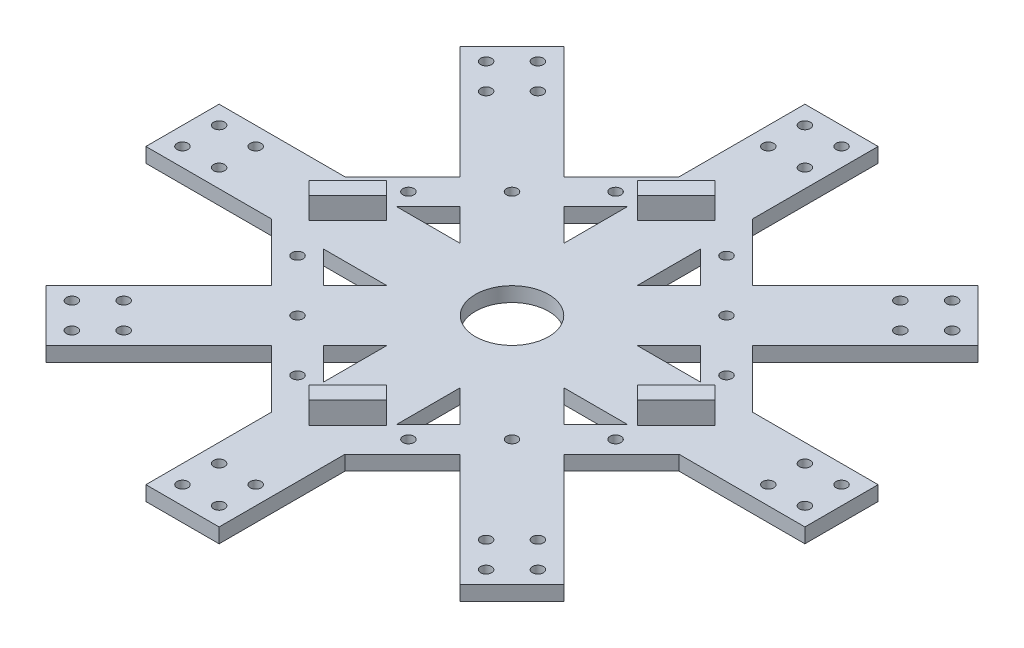
SolidWorks part; units mm, degrees
ref_plane "Front Plane" through (0, 0, 0) normal (0, 0, 1) x (1, 0, 0)
ref_plane "Top Plane" through (0, 0, 0) normal (0, 1, 0) x (1, 0, 0)
ref_plane "Right Plane" through (0, 0, 0) normal (1, 0, 0) x (0, 0, -1)
sketch "Sketch1" plane through (0, 0, 0) normal (0, 1, 0) x (1, 0, 0)
  line L0 (20, 100) -> (100, 100)
  line L1 (0, 0) -> (20, 0)
  line L2 (0, 0) -> (0, 80)
  line L3 (0, 180) -> (20, 180)
  line L4 (20, 0) -> (20, 80)
  line L5 (-80, 100) -> (0, 100)
  line L6 (-80, 100) -> (-80, 80)
  line L7 (-80, 80) -> (0, 80)
  line L8 (100, 100) -> (100, 80)
  line L9 (0, 100) -> (0, 180)
  line L10 (20, 80) -> (100, 80)
  line L11 (20, 100) -> (20, 180)
  line L12 (-40, 100) -> (0, 140) construction
  line L13 (20, 140) -> (60, 100) construction
  line L14 (60, 80) -> (20, 40) construction
  line L15 (0, 40) -> (-40, 80) construction
  line L16 (0, 48.4853) -> (-31.5147, 80)
  line L17 (51.5147, 80) -> (20, 48.4853)
  line L18 (20, 131.5147) -> (51.5147, 100)
  line L19 (-31.5147, 100) -> (0, 131.5147)
  line L20 (0, 34.3431) -> (-45.6569, 80)
  line L21 (65.6569, 80) -> (20, 34.3431)
  line L22 (20, 145.6569) -> (65.6569, 100)
  line L23 (-45.6569, 100) -> (0, 145.6569)
  line L24 (-2.8284, 37.1716) -> (-42.8284, 77.1716) construction
  line L25 (-35.7574, 95.7574) -> (4.2426, 135.7574) construction
  line L26 (15.7574, 135.7574) -> (55.7574, 95.7574) construction
  line L27 (55.7574, 84.2426) -> (15.7574, 44.2426) construction
  line L28 (4.2426, 44.2426) -> (-35.7574, 84.2426) construction
  line L29 (62.8284, 77.1716) -> (22.8284, 37.1716) construction
  line L30 (22.8284, 142.8284) -> (62.8284, 102.8284) construction
  line L31 (-42.8284, 102.8284) -> (-2.8284, 142.8284) construction
  circle A0 centre (10, 90) radius 1.5
  point P24 (10, 180)
  point P25 (100, 90)
  dimension "D13" = 3
  dimension "D2" = 180
  dimension "D3" = 180
  dimension "D4" = 20
  dimension "D7" = 40
  dimension "D8" = 40
  dimension "D9" = 40
  dimension "D10" = 40
  dimension "D11" = 6
  dimension "D12" = 4
extrude "Base" add sketch "Sketch1" along normal blind 4 contours L0 L11 L3 L9 L5 L6 L7 L2 L1 L4 L10 L8 | L23 L5 L19 L9 | L22 L11 L18 L0 | L20 L2 L16 L7 | L21 L10 L17 L4 region at (35.7574, 0, -97.4544) region at (39.5089, 0, -119.5089) region at (39.5089, 0, -60.4911) region at (-19.5089, 0, -119.5089) region at (-19.5089, 0, -60.4911)
sketch "Sketch2" plane through (0, 4, 0) normal (0, 1, 0) x (1, 0, 0)
  line L0 (40.5824, 165.4836) -> (-65.4836, 59.4176) construction
  line L1 (-65.4836, 59.4176) -> (-20.5824, 14.5164) construction
  line L2 (-20.5824, 14.5164) -> (85.4836, 120.5824) construction
  line L3 (85.4836, 120.5824) -> (40.5824, 165.4836) construction
  line L4 (15.3033, 50.402) -> (4.6967, 39.7954)
  line L5 (-22.7601, 57.2399) -> (42.1744, 122.1744) construction
  line L6 (4.6967, 39.7954) -> (8.2322, 36.2599)
  line L7 (20, 145.6569) -> (65.6569, 100) construction
  line L8 (0, 34.3431) -> (-45.6569, 80) construction
  line L9 (51.4142, 48.5858) -> (-13.5858, 113.5858) construction
  line L10 (8.2322, 36.2599) -> (18.8388, 46.8665)
  line L11 (18.8388, 46.8665) -> (15.3033, 50.402)
  line L12 (11.7678, 143.7401) -> (1.1612, 133.1335)
  line L13 (51.5147, 80) -> (20, 48.4853) construction
  line L14 (49.598, 84.6967) -> (60.2046, 95.3033)
  line L15 (60.2046, 95.3033) -> (63.7401, 91.7678)
  line L16 (63.7401, 91.7678) -> (53.1335, 81.1612)
  line L17 (53.1335, 81.1612) -> (49.598, 84.6967)
  line L18 (15.3033, 140.2046) -> (11.7678, 143.7401)
  line L19 (4.6967, 129.598) -> (15.3033, 140.2046)
  line L20 (1.1612, 133.1335) -> (4.6967, 129.598)
  line L21 (-43.7401, 88.2322) -> (-33.1335, 98.8388)
  line L22 (-40.2046, 84.6967) -> (-43.7401, 88.2322)
  line L23 (-29.598, 95.3033) -> (-40.2046, 84.6967)
  line L24 (-33.1335, 98.8388) -> (-29.598, 95.3033)
  point P7 (42.8284, 122.8284)
  point P11 (-22.8284, 57.1716)
  point P12 (63.033, 143.033)
  point P16 (35.7574, 64.2426)
  point P17 (-12.4506, 112.4506)
  point P20 (32.4506, 67.5494)
  point P22 (10, 45.0987)
  point P26 (54.9013, 90)
  point P27 (10, 90)
  dimension "D1" = 150
  dimension "D2" = 63.5
  dimension "D3" = 15
  dimension "D4" = 5
extrude "BatteryClip" add sketch "Sketch2" along normal blind 6
ref_axis "RotationalAxis" through (10, 4, -90) along (0, -1, 0)
ref_plane "Plane3" through (50, 0, -50) normal (-0.7071, 0, 0.7071) x (0.7071, 0, 0.7071)
sketch "Sketch6" plane through (0, 0, 0) normal (0, -1, 0) x (1, 0, 0)
  line L0 (66.5685, -160.7107) -> (10, -104.1421)
  line L1 (-60.7107, -33.4315) -> (-46.5685, -19.2893)
  line L2 (-46.5685, -19.2893) -> (10, -75.8579)
  line L3 (66.5685, -160.7107) -> (80.7107, -146.5685)
  line L4 (-46.5685, -160.7107) -> (10, -104.1421)
  line L5 (80.7107, -33.4315) -> (66.5685, -19.2893)
  line L6 (66.5685, -19.2893) -> (10, -75.8579)
  line L7 (-60.7107, -146.5685) -> (-46.5685, -160.7107)
  line L8 (10, -90) -> (75.7432, -155.7432) construction
  line L10 (51.5556, -48.4444) -> (48.4444, -51.5556) construction
  line L11 (-33.5468, -133.5468) -> (10, -90) construction
  line L12 (-4.1421, -90) -> (-60.7107, -146.5685)
  line L13 (10, -75.8579) -> (2.9289, -82.9289) construction
  line L14 (2.9289, -82.9289) -> (-4.1421, -90) construction
  line L15 (-4.1421, -90) -> (-60.7107, -33.4315)
  line L16 (2.9289, -97.0711) -> (-4.1421, -90) construction
  line L17 (10, -104.1421) -> (2.9289, -97.0711) construction
  line L18 (24.1421, -90) -> (80.7107, -33.4315)
  line L19 (10, -104.1421) -> (17.0711, -97.0711) construction
  line L20 (17.0711, -97.0711) -> (24.1421, -90) construction
  line L21 (17.0711, -82.9289) -> (45.7458, -54.2542) construction
  line L22 (10, -90) -> (17.0711, -82.9289) construction
  line L23 (24.1421, -90) -> (80.7107, -146.5685)
  line L24 (17.0711, -82.9289) -> (24.1421, -90) construction
  line L25 (10, -75.8579) -> (17.0711, -82.9289) construction
  point P15 (73.6396, -26.3604)
  point P17 (73.6396, -153.6396)
  dimension "D1" = 180
  dimension "D2" = 20
extrude "Boss-Extrude1" add sketch "Sketch6" against normal up to surface (4 mm away) up to face at (10, 4, -90)
hole_wizard "Ø3.0mm Dowel Hole2" positions "3DSketch2" profile "Sketch5" hole size "Ø3.0" standard "ANSI Metric" end condition through all
sketch3d "3DSketch2"
  line L1 (10, 4, 0) -> (10, 4, -50000) construction
  line L2 (0, 4, 0) -> (20, 4, 0) construction
  line L3 (0, 4, -180) -> (20, 4, -180) construction
  line L4 (-65, 4, -90) -> (49935, 4, -90) construction
  line L5 (-80, 4, -100) -> (-80, 4, -80) construction
  line L6 (100, 4, -100) -> (100, 4, -80) construction
  line L7 (-8.7317, 4, -71.2683) -> (30646.88, 4, -30726.88) construction
  line L11 (-5.1508, 4, -46.565) -> (-33.435, 4, -74.8492) construction
  line L13 (0, 4, -48.4853) -> (-8.6863, 4, -57.1716) construction
  line L14 (-46.5685, 4, -19.2893) -> (-60.7107, 4, -33.4315) construction
  line L15 (-15.7574, 4, -50.1005) -> (-46.5685, 4, -19.2893) construction
  line L16 (-53.6396, 4, -33.4315) -> (-46.5685, 4, -40.5025) construction
  line L17 (-46.5685, 4, -40.5025) -> (-39.4975, 4, -33.4315) construction
  line L18 (-39.4975, 4, -33.4315) -> (-46.5685, 4, -26.3604) construction
  line L19 (-46.5685, 4, -26.3604) -> (-53.6396, 4, -33.4315) construction
  line L21 (-60.7107, 4, -33.4315) -> (-29.8995, 4, -64.2426) construction
  line L22 (66.5685, 4, -160.7107) -> (80.7107, 4, -146.5685) construction
  point P0 (5, 4, -5)
  point P2 (5, 4, -15)
  point P4 (15, 4, -15)
  point P6 (15, 4, -5)
  point P17 (10, 4, 0)
  point P20 (10, 4, -180)
  point P27 (-80, 4, -90)
  point P30 (100, 4, -90)
  point P44 (-5.1508, 4, -46.565)
  point P46 (-19.2929, 4, -60.7071)
  point P48 (-33.435, 4, -74.8492)
  point P74 (-53.6396, 4, -33.4315)
  point P76 (-46.5685, 4, -40.5025)
  point P78 (-39.4975, 4, -33.4315)
  point P80 (-46.5685, 4, -26.3604)
  point P98 (73.6396, 4, -153.6396)
  point P100 (-53.6396, 4, -26.3604)
  dimension "D1" = 5
  dimension "D6" = 40
  dimension "D2" = 10
  dimension "D3" = 10
  dimension "D4" = 5
  dimension "D5" = 5
  dimension "D7" = 10
  dimension "D8" = 10
  dimension "D9" = 5
  dimension "D10" = 5
sketch "Sketch5" plane through (5, 4, -5) normal (1, 0, 0) x (0, 0, 1)
  line L0 (0, 0) -> (0, 4)
  line L1 (0, 4) -> (1.5, 4)
  line L2 (1.5, 4) -> (1.5, 0)
  line L5 (1.5, 0) -> (0, 0)
  line L11 (0, -6.35) -> (0, 107.95) construction
  dimension "Thru Hole Dia." = 3
  dimension "Thru Hole Depth" = 4
pattern_circular "CirPattern2" count 4 over 360 about axis through (10, 4, -90) along (0, -1, 0) of "Ø3.0mm Dowel Hole2"
sketch "Sketch7" plane through (0, 4, 0) normal (0, 1, 0) x (1, 0, 0)
  circle A0 centre (10, 90) radius 10
  dimension "D1" = 20
extrude "Refrerence" cut sketch "Sketch7" against normal blind 10
